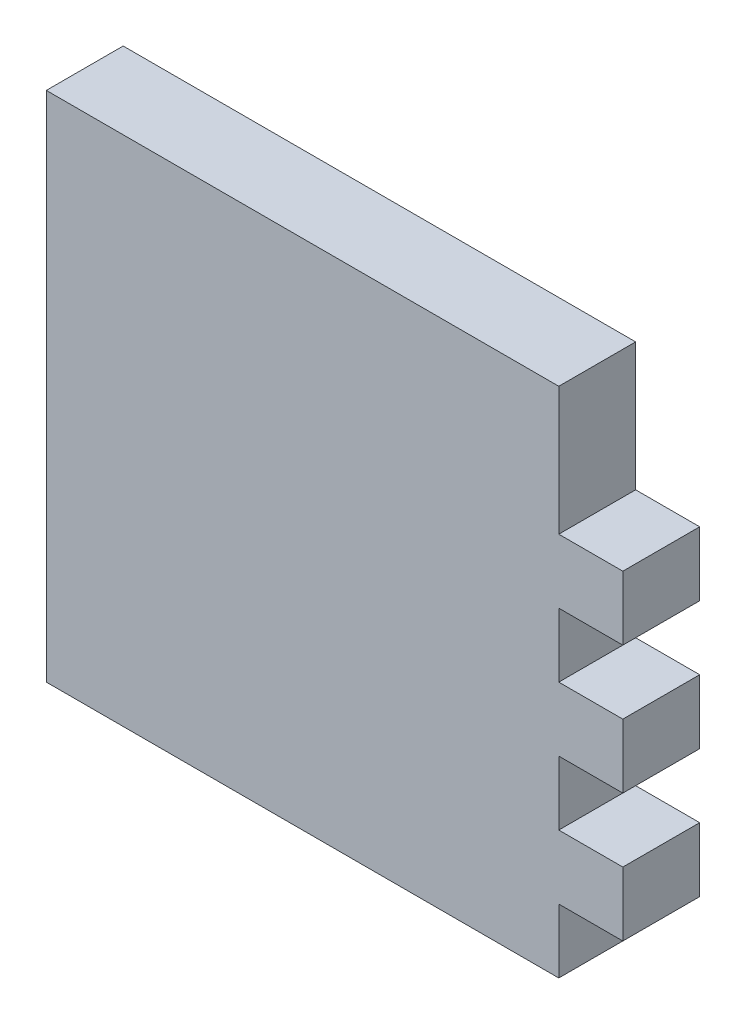
SolidWorks part; units mm, degrees
ref_plane "Front Plane" through (0, 0, 0) normal (0, 0, 1) x (1, 0, 0)
ref_plane "Top Plane" through (0, 0, 0) normal (0, 1, 0) x (1, 0, 0)
ref_plane "Right Plane" through (0, 0, 0) normal (1, 0, 0) x (0, 0, -1)
sketch "Sketch1" plane through (0, 0, 0) normal (0, 0, 1) x (1, 0, 0)
  line L1 (-12.6866, 14.403) -> (27.3134, 14.403)
  line L2 (-12.6866, 14.403) -> (-12.6866, -25.597)
  line L3 (-12.6866, -25.597) -> (27.3134, -25.597)
  line L4 (27.3134, 14.403) -> (27.3134, -25.597)
  line L5 (27.3134, 4.403) -> (32.3134, 4.403)
  line L6 (27.3134, 4.403) -> (27.3134, -0.597)
  line L7 (27.3134, -0.597) -> (32.3134, -0.597)
  line L8 (32.3134, 4.403) -> (32.3134, -0.597)
  line L9 (27.3134, -10.597) -> (32.3134, -10.597)
  line L10 (27.3134, -10.597) -> (27.3134, -5.597)
  line L11 (27.3134, -5.597) -> (32.3134, -5.597)
  line L12 (32.3134, -10.597) -> (32.3134, -5.597)
  line L13 (27.3134, -20.597) -> (32.3134, -20.597)
  line L14 (27.3134, -20.597) -> (27.3134, -15.597)
  line L15 (27.3134, -15.597) -> (32.3134, -15.597)
  line L16 (32.3134, -20.597) -> (32.3134, -15.597)
  dimension "D1" = 40
  dimension "D2" = 40
  dimension "D3" = 5
  dimension "D4" = 5
  dimension "D5" = 5
  dimension "D6" = 5
  dimension "D7" = 5
  dimension "D8" = 5
  dimension "D9" = 10
  dimension "D10" = 5
  dimension "D11" = 5
extrude "Boss-Extrude1" add sketch "Sketch1" along normal blind 6 contours L4 L1 L2 L3 region at (7.3134, -5.597, 0)
extrude "Boss-Extrude2" add sketch "Sketch1<4>" along normal blind 6 contours L8 L5 L4 L7 | L9 L12 L11 L4 | L13 L16 L15 L4 region at (29.8134, 1.903, 0) region at (29.8134, -18.097, 0) region at (29.8134, -8.097, 0)
sketch "Sketch1<4>" plane through (0, 0, 0) normal (0, 0, 1) x (1, 0, 0) same geometry as "Sketch1"
